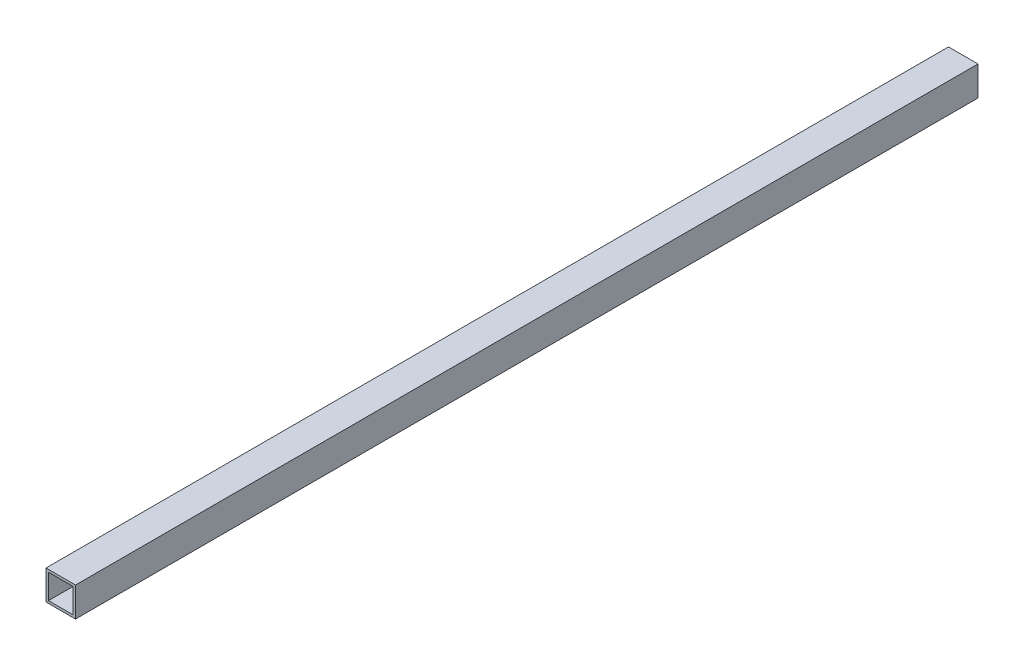
SolidWorks part; units mm, degrees
ref_plane "Front" through (0, 0, 0) normal (0, 0, 1) x (1, 0, 0)
ref_plane "Top" through (0, 0, 0) normal (0, 1, 0) x (1, 0, 0)
ref_plane "Right" through (0, 0, 0) normal (1, 0, 0) x (0, 0, -1)
sketch "Sketch1" plane through (0, 0, 0) normal (0, 0, 1) x (1, 0, 0)
  line L1 (-18.9342, 14.9139) -> (0.1158, 14.9139)
  line L2 (-18.9342, 14.9139) -> (-18.9342, -4.1361)
  line L3 (-18.9342, -4.1361) -> (0.1158, -4.1361)
  line L4 (0.1158, 14.9139) -> (0.1158, -4.1361)
  dimension "D1" = 19.05
  dimension "D2" = 19.05
extrude "Boss-Extrude1" add sketch "Sketch1" along normal blind 582.676
sketch "Sketch2" plane through (0, 0, 0) normal (0, 0, -1) x (-1, 0, 0)
  line L8 (17.3467, -2.5486) -> (17.3467, 13.3264)
  line L9 (17.3467, 13.3264) -> (1.4717, 13.3264)
  line L10 (1.4717, 13.3264) -> (1.4717, -2.5486)
  line L11 (1.4717, -2.5486) -> (17.3467, -2.5486)
  line L12 (17.3467, -2.5486) -> (17.3467, 13.3264)
  line L13 (17.3467, 13.3264) -> (1.4717, 13.3264)
  line L14 (1.4717, 13.3264) -> (1.4717, -2.5486)
  line L15 (1.4717, -2.5486) -> (17.3467, -2.5486)
  dimension "D1" = 1.5875
extrude "Cut-Extrude1" cut sketch "Sketch2" against normal through all
